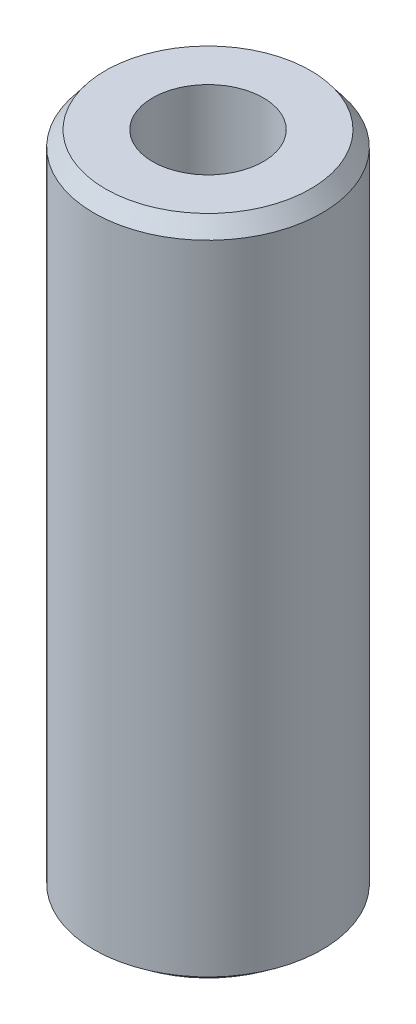
SolidWorks part; units mm, degrees
ref_plane "Front Plane" through (0, 0, 0) normal (0, 0, 1) x (1, 0, 0)
ref_plane "Top Plane" through (0, 0, 0) normal (0, 1, 0) x (1, 0, 0)
ref_plane "Right Plane" through (0, 0, 0) normal (1, 0, 0) x (0, 0, -1)
sketch "Sketch1" plane through (0, 0, 0) normal (0, 1, 0) x (1, 0, 0)
  circle A0 centre (0, 0) radius 10
  dimension "SHAFT_OD" = 20
extrude "Boss-Extrude1" add sketch "Sketch1" along normal blind 58.2443
sketch "Sketch2" plane through (0, 0, 0) normal (0, 1, 0) x (1, 0, 0)
  circle A0 centre (0, 0) radius 4.8503
  dimension "BORE_D" = 9.7006
extrude "Cut-Extrude1" cut sketch "Sketch2" along normal through all
chamfer "Chamfer1" distance 1.3219 angle 37.469 2 edges at (0, 58.2443, 10) (0, 0, 10) first distance on face at (0, 58.2443, 10) first distance on face at (0, 0, 4.8503)
